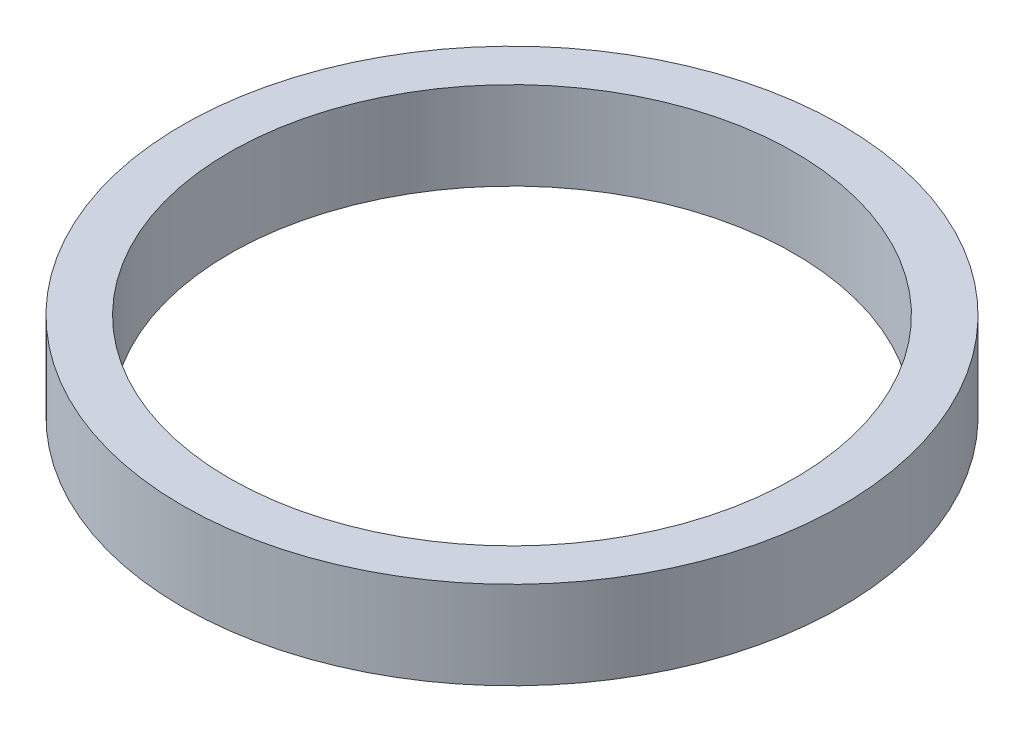
SolidWorks part; units mm, degrees
ref_plane "Front Plane" through (0, 0, 0) normal (0, 0, 1) x (1, 0, 0)
ref_plane "Top Plane" through (0, 0, 0) normal (0, 1, 0) x (1, 0, 0)
ref_plane "Right Plane" through (0, 0, 0) normal (1, 0, 0) x (0, 0, -1)
sketch "Sketch1" plane through (0, 0, 0) normal (0, 1, 0) x (1, 0, 0)
  circle A0 centre (0, 0) radius 52.5
  dimension "FLANGE_OD" = 105
extrude "Boss-Extrude1" add sketch "Sketch1" along normal blind 14
sketch "Sketch2" plane through (0, 0, 0) normal (0, 1, 0) x (1, 0, 0)
  circle A0 centre (0, 0) radius 45
  dimension "BORE_D" = 90
extrude "Cut-Extrude1" cut sketch "Sketch2" along normal through all
sketch "Sketch3" plane through (0, 14, 0) normal (0, 1, 0) x (1, 0, 0)
  circle A0 centre (0, 0) radius 23.8352 construction
  circle A1 centre (-23.8352, 0) radius 1.5
  dimension "BOLT_D" = 3
  dimension "BOLT_PCD" = 47.6703
extrude "Cut-Extrude2" cut sketch "Sketch3" against normal blind 10.2701 rebuild error yes
pattern_circular "CirPattern1" count 8 over 360 rebuild error yes
